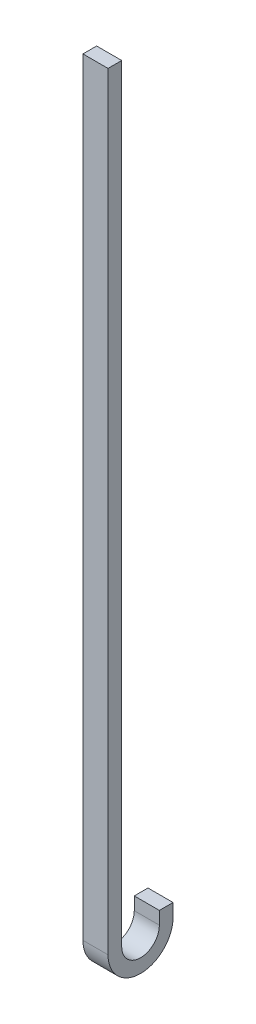
SolidWorks part; units mm, degrees
ref_plane "Front" through (0, 0, 0) normal (0, 0, 1) x (1, 0, 0)
ref_plane "Top" through (0, 0, 0) normal (0, 1, 0) x (1, 0, 0)
ref_plane "Right" through (0, 0, 0) normal (1, 0, 0) x (0, 0, -1)
sketch "Sketch1" plane through (0, 0, 0) normal (1, 0, 0) x (0, 0, -1)
  line L0 (0, 0) -> (0, -839.4925)
  line L1 (71.12, -839.4925) -> (71.12, -825.5)
  line L2 (14.986, 0) -> (14.986, -839.4925)
  line L3 (56.134, -839.4925) -> (56.134, -825.5)
  line L4 (0, 0) -> (14.986, 0)
  line L5 (56.134, -825.5) -> (71.12, -825.5)
  line L7 (88.9, -901.7) -> (0, -901.7) construction
  arc A0 (0, -839.4925) -> (71.12, -839.4925) centre (35.56, -839.4925) ccw
  arc A1 (14.986, -839.4925) -> (56.134, -839.4925) centre (35.56, -839.4925) ccw
  dimension "D1" = 965.2
  dimension "D2" = 71.12
  dimension "D4" = 41.148
  dimension "D5" = 76.2
  dimension "D3" = 14.986
extrude "Boss-Extrude1" add sketch "Sketch1" along normal blind 27.432
